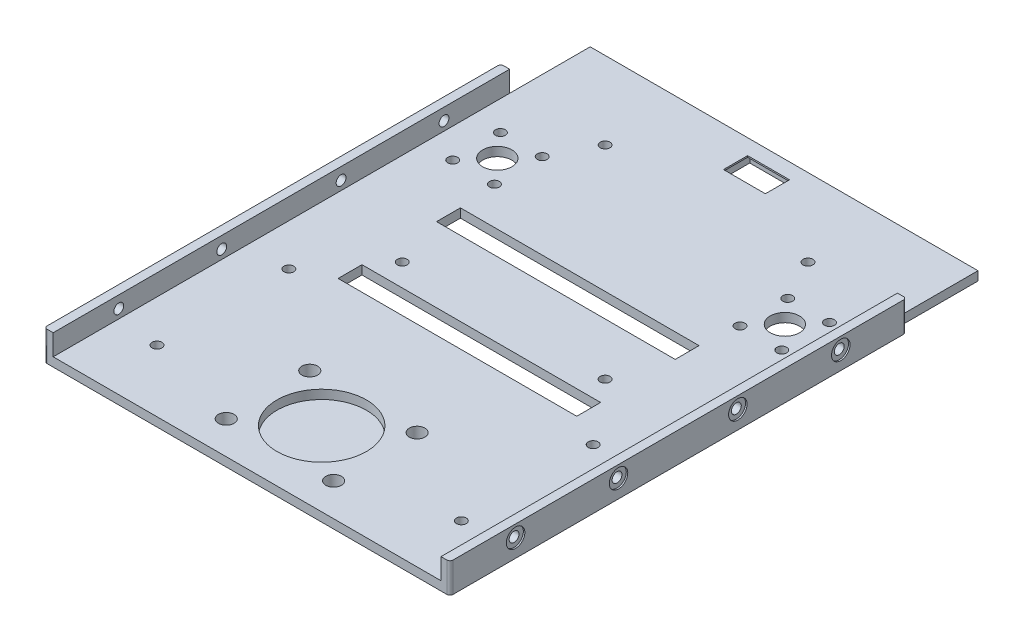
SolidWorks part; units mm, degrees
ref_plane "前视基准面" through (0, 0, 0) normal (0, 0, 1) x (1, 0, 0)
ref_plane "上视基准面" through (0, 0, 0) normal (0, 1, 0) x (1, 0, 0)
ref_plane "右视基准面" through (0, 0, 0) normal (1, 0, 0) x (0, 0, -1)
sketch "草图1" plane through (0, 0, 0) normal (0, 1, 0) x (1, 0, 0)
  line L1 (-65, -90) -> (65, -90)
  line L2 (-65, -90) -> (-65, 90)
  line L3 (-65, 90) -> (65, 90)
  line L4 (65, -90) -> (65, 90)
  line L5 (-65, -90) -> (65, 90) construction
  line L6 (-65, 90) -> (65, -90) construction
  line L7 (0, 0) -> (0, -102.1022) construction
  line L9 (-40, -13.5) -> (40, -13.5)
  line L10 (-40, -13.5) -> (-40, -17.5)
  line L11 (-40, -17.5) -> (40, -17.5)
  line L12 (40, -13.5) -> (40, -17.5)
  line L13 (0, -17.5) -> (0, -13.5) construction
  line L14 (-40, -15.5) -> (40, -15.5) construction
  line L15 (0, 0) -> (0, 95.4452) construction
  line L16 (-40, 19.5) -> (40, 19.5)
  line L17 (-40, 19.5) -> (-40, 15.5)
  line L18 (-40, 15.5) -> (40, 15.5)
  line L19 (40, 19.5) -> (40, 15.5)
  line L20 (0, 15.5) -> (0, 19.5) construction
  line L21 (-40, 17.5) -> (40, 17.5) construction
  circle A5 centre (41.15, 34.0637) radius 1.65
  circle A6 centre (55.15, 34.0637) radius 1.65
  circle A7 centre (48.2, 42.0637) radius 4.9
  circle A8 centre (41.15, 50.0637) radius 1.65
  circle A9 centre (55.15, 50.0637) radius 1.65
  circle A15 centre (-18, -51) radius 2.625
  circle A16 centre (18, -51) radius 2.625
  circle A17 centre (18, -79) radius 2.625
  circle A18 centre (-18, -79) radius 2.625
  circle A19 centre (0, -65) radius 15
  circle A20 centre (-41.15, 34.0637) radius 1.65
  circle A21 centre (-55.15, 34.0637) radius 1.65
  circle A22 centre (-55.15, 50.0637) radius 1.65
  circle A23 centre (-48.2, 42.0637) radius 4.9
  circle A24 centre (-41.15, 50.0637) radius 1.65
  point P0 (0, 0)
  point P5 (0, 17.5)
  point P35 (0, -65)
  point P38 (0, -15.5)
  dimension "D3" = 9.8
  dimension "D4" = 3.3
  dimension "D8" = 5.25
  dimension "D11" = 30
  dimension "D15" = 4
  dimension "D1" = 130
  dimension "D2" = 180
  dimension "D5" = 65
  dimension "D6" = 14
  dimension "D7" = 14
  dimension "D9" = 36
  dimension "D10" = 28
  dimension "D12" = 4
  dimension "D13" = 80
  dimension "D14" = 15.5
  dimension "D16" = 80
  dimension "D17" = 15.5
extrude "凸台-拉伸1" add sketch "草图1" along normal blind 3
sketch "草图3" plane through (0, 0, 0) normal (0, 1, 0) x (1, 0, 0)
  line L0 (0, 0) -> (0, 98.2617) construction
  line L1 (0, 0) -> (77.91, 0) construction
  line L2 (65, 90) -> (-65, 90) construction
  line L3 (-30, -10) -> (30, -10)
  line L4 (-40, 0) -> (-40, 60)
  line L5 (-30, 70) -> (30, 70)
  line L6 (40, 0) -> (40, 60)
  line L7 (-40, -10) -> (40, 70) construction
  line L8 (-40, 70) -> (40, -10) construction
  line L9 (0, 0) -> (0, -104.5321) construction
  line L15 (-56, -20) -> (56, -20)
  line L16 (-54, -22) -> (54, -22)
  line L20 (-54, -22) -> (-54, -72.2)
  line L21 (-54, -72.2) -> (54, -72.2)
  line L22 (54, -22) -> (54, -72.2)
  line L23 (-54, -22) -> (54, -72.2) construction
  line L24 (-54, -72.2) -> (54, -22) construction
  line L25 (56, -20) -> (56, -74.2)
  line L26 (-56, -74.2) -> (56, -74.2)
  line L27 (-56, -20) -> (-56, -74.2)
  circle A0 centre (-34, 64) radius 1.65
  circle A1 centre (-34, -4) radius 1.65
  circle A2 centre (34, -4) radius 1.65
  circle A3 centre (34, 64) radius 1.65
  arc A4 (-30, -10) -> (-40, 0) centre (-30, 0) cw
  arc A5 (30, -10) -> (40, 0) centre (30, 0) ccw
  arc A6 (30, 70) -> (40, 60) centre (30, 60) cw
  arc A7 (-40, 60) -> (-30, 70) centre (-30, 60) cw
  circle A8 centre (-51, -25) radius 1.65
  circle A9 centre (-51.0044, -69.2) radius 1.65
  circle A10 centre (51.0044, -69.2) radius 1.65
  circle A11 centre (51, -25) radius 1.65
  point P3 (0, 30)
  point P11 (0, -47.1)
  point P43 (0, -47.1)
  dimension "D8" = 3.3
  dimension "D11" = 10
  dimension "D12" = 3.3
  dimension "D13" = 2.9956
  dimension "D1" = 80
  dimension "D2" = 80
  dimension "D3" = 20
  dimension "D4" = 108
  dimension "D5" = 50.2
  dimension "D6" = 2
  dimension "D7" = 10
  dimension "D9" = 6
  dimension "D10" = 6
  dimension "D14" = 3
  dimension "D15" = 3
  dimension "D16" = 3
extrude "切除-拉伸2" cut sketch "草图3" along normal through all contours A8 | A9 | A10 | A11 | A2 | A3 | A0 | A1
sketch "草图4" plane through (0, 0, 0) normal (0, -1, 0) x (1, 0, 0)
  line L0 (0, 0) -> (0, -93.2535) construction
  line L1 (65, -90) -> (-65, -90) construction
  line L2 (-7.5, -75.5) -> (7.5, -75.5)
  line L3 (-7.5, -75.5) -> (-7.5, -86)
  line L4 (-7.5, -86) -> (7.5, -86)
  line L5 (7.5, -75.5) -> (7.5, -86)
  line L6 (0, -86) -> (0, -75.5) construction
  line L7 (-7.5, -80.75) -> (7.5, -80.75) construction
  point P3 (0, -80.75)
  dimension "D1" = 10.5
  dimension "D2" = 15
  dimension "D3" = 4
extrude "切除-拉伸3" cut sketch "草图4" against normal blind 2.51
sketch "草图5" plane through (0, 2.51, 0) normal (0, -1, 0) x (1, 0, 0)
  line L0 (0, 0) -> (0, -103.6754) construction
  line L1 (-7.5, -86) -> (7.5, -86) construction
  line L2 (-7.025, -76.7) -> (7.025, -76.7)
  line L3 (-7.025, -76.7) -> (-7.025, -84.8)
  line L4 (-7.025, -84.8) -> (7.025, -84.8)
  line L5 (7.025, -76.7) -> (7.025, -84.8)
  line L6 (0, -84.8) -> (0, -76.7) construction
  line L7 (-7.025, -80.75) -> (7.025, -80.75) construction
  point P3 (0, -80.75)
  dimension "D1" = 8.1
  dimension "D2" = 14.05
  dimension "D3" = 1.2
extrude "切除-拉伸4" cut sketch "草图5" against normal blind 0.49
sketch "草图6" plane through (0, 0, 0) normal (0, 0, 1) x (1, 0, 0)
  line L0 (-25, 0) -> (-25, -1)
  line L1 (-65, 0) -> (65, 0) construction
  line L2 (-25, -1) -> (25, -1)
  line L3 (0, -1) -> (0, 0)
  line L4 (25, 0) -> (-25, 0)
  line L5 (25, 0) -> (25, -1)
  dimension "D1" = 1
  dimension "D2" = 25
extrude "凸台-拉伸2" add sketch "草图6" along normal blind 40 from offset 45 contours L3 L4 L0 L2 | L5 L4 L3 L2 region at (-12.5, -0.5, 0) region at (12.5, -0.5, 0)
sketch "草图9" plane through (0, -1, 0) normal (0, -1, 0) x (1, 0, 0)
  line L0 (25, 85) -> (25, 45) construction
  line L1 (-25, 45) -> (25, 45) construction
  circle A0 centre (-18, 51) radius 2.625
  circle A1 centre (18, 51) radius 2.625
  circle A2 centre (-18, 79) radius 2.625
  circle A3 centre (18, 79) radius 2.625
  dimension "D1" = 5.25
  dimension "D2" = 7
  dimension "D3" = 6
extrude "切除-拉伸5" cut sketch "草图9" against normal blind 1
sketch "草图10" plane through (0, 3, 0) normal (0, 1, 0) x (1, 0, 0)
  line L0 (-65, 63) -> (-67, 63)
  line L1 (-65, 90) -> (-65, -90) construction
  line L2 (-68, 62) -> (-68, -89)
  line L3 (-67, -90) -> (-65, -90)
  line L4 (-65, -90) -> (-65, 63)
  line L5 (65, 90) -> (-65, 90) construction
  line L6 (0, 0) -> (0, 97.9495) construction
  line L7 (65, -90) -> (65, 63)
  line L8 (67, -90) -> (65, -90)
  line L9 (68, 62) -> (68, -89)
  line L10 (65, 63) -> (67, 63)
  arc A0 (-67, 63) -> (-68, 62) centre (-67, 62) ccw
  arc A1 (-68, -89) -> (-67, -90) centre (-67, -89) ccw
  arc A2 (68, -89) -> (67, -90) centre (67, -89) cw
  arc A3 (67, 63) -> (68, 62) centre (67, 62) cw
  dimension "D3" = 1
  dimension "D1" = 27
  dimension "D2" = 3
extrude "凸台-拉伸3" add sketch "草图10" along normal blind 10 from offset 3 offset against normal yes
sketch "草图11" plane through (68, 0, 0) normal (1, 0, 0) x (0, 0, -1)
  line L0 (62, 0) -> (-89, 0) construction
  line L1 (-13.5, 0) -> (-13.5, 36.6307) construction
  line L3 (-89, 0) -> (62, 0) construction
  line L4 (-90, 10) -> (-90, 0) construction
  circle A0 centre (-33.5, 6) radius 1.65
  circle A1 centre (-68, 6) radius 1.65
  circle A2 centre (6.5, 6) radius 1.65
  circle A3 centre (41, 6) radius 1.65
  dimension "D1" = 6
  dimension "D5" = 3.3
  dimension "D6" = 3.3
  dimension "D2" = 6
  dimension "D3" = 20
  dimension "D4" = 22
extrude "切除-拉伸6" cut sketch "草图11" against normal up to surface (3 mm away) up to face at (65, 6.5, 13.5)
mirror "镜向1" about plane through (0, 0, 0) normal (1, 0, 0) of "切除-拉伸6"
sketch "草图12" plane through (68, 0, 0) normal (1, 0, 0) x (0, 0, -1)
  circle A0 centre (-68, 6) radius 3.1
  circle A1 centre (-33.5, 6) radius 3.1
  circle A2 centre (6.5, 6) radius 3.1
  circle A3 centre (41, 6) radius 3.1
  dimension "D1" = 6.2
extrude "切除-拉伸7" cut sketch "草图12" against normal blind 0.5
mirror "镜向3" about plane through (0, 0, 0) normal (1, 0, 0) of "切除-拉伸7"
sketch "草图13" plane through (0, 3, 0) normal (0, 1, 0) x (1, 0, 0)
  line L0 (40, -17.5) -> (40, -13.5) construction
  line L1 (-40, -11.5) -> (40, -11.5)
  line L2 (-40, -11.5) -> (-40, -19.5)
  line L3 (-40, -19.5) -> (40, -19.5)
  line L4 (40, -11.5) -> (40, -19.5)
  line L5 (0, -19.5) -> (0, -11.5) construction
  line L6 (-40, -15.5) -> (40, -15.5) construction
  line L8 (-40, 21.5) -> (40, 21.5)
  line L9 (-40, 21.5) -> (-40, 13.5)
  line L10 (-40, 13.5) -> (40, 13.5)
  line L11 (40, 21.5) -> (40, 13.5)
  line L12 (0, 13.5) -> (0, 21.5) construction
  line L13 (-40, 17.5) -> (40, 17.5) construction
  point P0 (0, -15.5)
  point P4 (0, 17.5)
  point P11 (40, 17.5)
  point P12 (0, 17.5)
  point P15 (-40, 17.5)
  point P16 (0, 17.5)
  dimension "D1" = 80
  dimension "D2" = 8
  dimension "D3" = 15.5
  dimension "D4" = 17.5
  dimension "D5" = 80
  dimension "D6" = 8
  dimension "D7" = 40
extrude "切除-拉伸8" cut sketch "草图13" against normal up to surface (3 mm away) up to face at (0, 0, 65)
